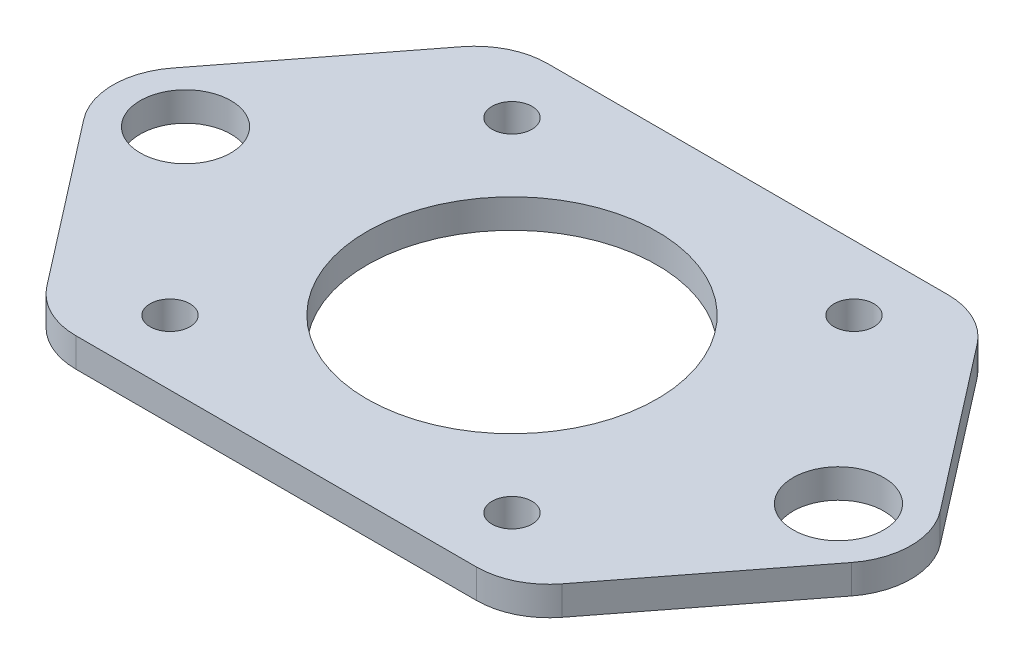
SolidWorks part; units mm, degrees
ref_plane "Front Plane" through (0, 0, 0) normal (0, 0, 1) x (1, 0, 0)
ref_plane "Top Plane" through (0, 0, 0) normal (0, 1, 0) x (1, 0, 0)
ref_plane "Right Plane" through (0, 0, 0) normal (1, 0, 0) x (0, 0, -1)
sketch "Sketch1" plane through (0, 0, 0) normal (0, 1, 0) x (1, 0, 0)
  line L0 (32.5, 32.5) -> (52.9094, 6.119)
  line L1 (-32.5, -32.5) -> (32.5, -32.5)
  line L3 (-32.5, 32.5) -> (32.5, 32.5)
  line L5 (-32.5, -32.5) -> (32.5, 32.5) construction
  line L6 (-32.5, 32.5) -> (32.5, -32.5) construction
  line L7 (32.5, -32.5) -> (52.9094, -6.119)
  line L8 (-32.5, 32.5) -> (-52.9094, 6.119)
  line L9 (-32.5, -32.5) -> (-52.9094, -6.119)
  circle A0 centre (0, 0) radius 20
  circle A1 centre (-23.57, 23.57) radius 2.75
  circle A2 centre (23.57, 23.57) radius 2.75
  circle A3 centre (23.57, -23.57) radius 2.75
  circle A4 centre (-23.57, -23.57) radius 2.75
  circle A5 centre (-45, 0) radius 6.25
  circle A6 centre (45, 0) radius 6.25
  arc A7 (-52.9094, 6.119) -> (-52.9094, -6.119) centre (-45, 0) ccw
  arc A8 (52.9094, -6.119) -> (52.9094, 6.119) centre (45, 0) ccw
  point P14 (0, 0)
  dimension "D1" = 40
  dimension "D2" = 5.5
  dimension "D8" = 12.5
  dimension "D9" = 12.5
  dimension "D12" = 20
  dimension "D13" = 20
  dimension "D14" = 65
  dimension "D3" = 23.57
  dimension "D4" = 23.57
  dimension "D6" = 47.14
  dimension "D7" = 65
  dimension "D10" = 90
  dimension "D11" = 45
  dimension "D15" = 32.5
  dimension "D5" = 4
base flange "Base-Flange1" sketch "Sketch1" thickness 4 reverse thickness direction no parameters "D1"=0.7366
fillet "Fillet1" radius 10 4 edges at (-32.5, -2, -32.5) (32.5, -2, -32.5) (32.5, -2, 32.5) (-32.5, -2, 32.5)
sketch "Bend-Lines1" [suppressed] plane through (0, 0, 0) normal (0, 1, 0) x (-1, 0, 0)
sketch "Bounding-Box1" [suppressed] plane through (0, 0, 0) normal (0, 1, 0) x (-1, 0, 0)
sheet metal parameters "Sheet-Metal1" thickness 4 parameters "D1"=0.7366
flat pattern "Flat-Pattern1" [suppressed]
sketch "Bend-Lines2" plane through (0, 0, 0) normal (0, 1, 0) x (-1, 0, 0)
sketch3d "Bounding-Box2" [suppressed]
  line L0 (10, -32.5, 0) -> (-100, -32.5, 0) construction
  line L1 (10, 32.5, 0) -> (-100, 32.5, 0) construction
  line L2 (10, -32.5, 0) -> (10, 32.5, 0) construction
  line L3 (-100, -32.5, 0) -> (-100, 32.5, 0) construction
